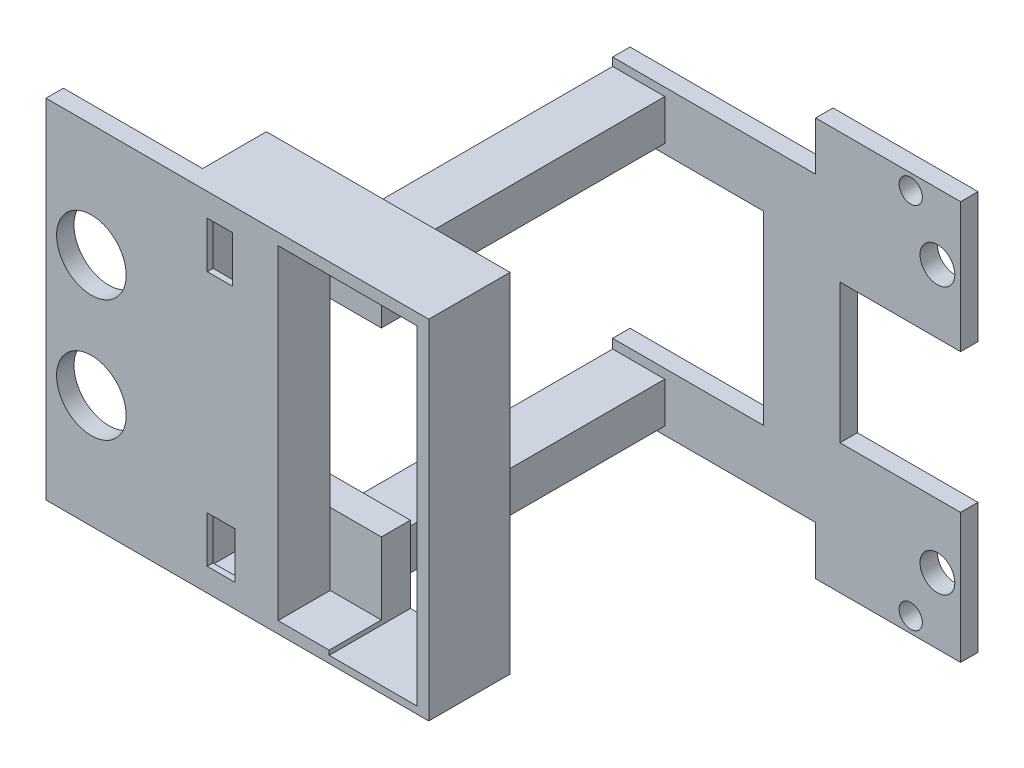
SolidWorks part; units mm, degrees
ref_plane "Front Plane" through (0, 0, 0) normal (0, 0, 1) x (1, 0, 0)
ref_plane "Top Plane" through (0, 0, 0) normal (0, 1, 0) x (1, 0, 0)
ref_plane "Right Plane" through (0, 0, 0) normal (1, 0, 0) x (0, 0, -1)
sketch "Sketch2" plane through (0, 0, 0) normal (0, 0, 1) x (1, 0, 0)
  line L0 (55, 0) -> (-55, 0) construction
  line L1 (-10.5, 15) -> (10.5, 15)
  line L2 (-10.5, 15) -> (-10.5, -15)
  line L3 (-10.5, -15) -> (10.5, -15)
  line L4 (10.5, 15) -> (10.5, -15)
  line L5 (0, -55) -> (0, 55) construction
  point P6 (-10.5, 0)
  point P7 (0, 15)
  dimension "D1" = 30
  dimension "D2" = 21
extrude "Boss-Extrude1" add sketch "Sketch2" along normal blind 7
sketch "Sketch3" plane through (0, 0, 7) normal (0, 0, 1) x (1, 0, 0)
  line L0 (-10.5, 15) -> (-10.5, -15) construction
  line L1 (-2.5, 14) -> (9.5, 14)
  line L2 (-2.5, 14) -> (-2.5, -14)
  line L3 (-2.5, -14) -> (9.5, -14)
  line L4 (9.5, 14) -> (9.5, -14)
  line L6 (10.5, -15) -> (10.5, 15) construction
  line L7 (10.5, 15) -> (-10.5, 15) construction
  line L8 (-10.5, -15) -> (10.5, -15) construction
  dimension "D1" = 8
  dimension "D2" = 1
  dimension "D3" = 1
  dimension "D4" = 1
extrude "Cut-Extrude1" cut sketch "Sketch3" against normal offset from surface (4.5 mm away) 2.5 up to face at (0, 0, 0)
sketch "Sketch4" plane through (0, 0, 0) normal (0, 0, -1) x (-1, 0, 0)
  line L0 (10.5, 15) -> (10.5, -15) construction
  line L1 (5.2688, 14) -> (9.5, 14)
  line L2 (5.2688, 14) -> (5.2688, -14)
  line L3 (5.2688, -14) -> (9.5, -14)
  line L4 (9.5, 14) -> (9.5, -14)
  line L5 (-10.5, 15) -> (10.5, 15) construction
  line L6 (10.5, -15) -> (-10.5, -15) construction
  dimension "D1" = 1
  dimension "D2" = 1
  dimension "D3" = 1
extrude "Cut-Extrude2" cut sketch "Sketch4" against normal offset from surface (6.5 mm away) 0.5 up to face at (3.5, 0, 7)
sketch "Sketch6" plane through (9.5, 0, 0) normal (-1, 0, 0) x (0, 0, 1)
  line L0 (7, 15) -> (7, -15) construction
  line L1 (7, 14) -> (6.5, 14)
  line L2 (7, 14) -> (7, 11.5)
  line L3 (7, 11.5) -> (6.5, 11.5)
  line L4 (6.5, 14) -> (6.5, 11.5)
  line L5 (2.5, 14) -> (7, 14) construction
  line L6 (7, 0) -> (0, 0.978) construction
  line L7 (7, -14) -> (7, 14) construction
  line L8 (3.8481, -11.0596) -> (3.3672, -10.9226)
  line L9 (3.1628, -13.4639) -> (3.8481, -11.0596)
  line L10 (3.1628, -13.4639) -> (2.682, -13.3268)
  line L11 (2.682, -13.3268) -> (3.3672, -10.9226)
  line L12 (0, -11.55) -> (0, 11.55) construction
  point P6 (6.75, 14)
  point P14 (7, 0)
  dimension "D1" = 0.5
  dimension "D2" = 2.5
sketch "Sketch7" plane through (0, 0, 7) normal (0, 0, 1) x (1, 0, 0)
  line L0 (-8.6, 9) -> (-6.4, 9)
  line L1 (-8.6, 13) -> (-6.4, 13)
  line L3 (-8.6, -13) -> (-6.2, -13)
  line L5 (-8.6, -9) -> (-6.2, -9)
  line L6 (-10.5, -15) -> (10.5, -15) construction
  line L7 (10.5, 15) -> (-10.5, 15) construction
  line L8 (-8.6, 13) -> (-8.6, 9)
  line L9 (-6.4, 13) -> (-6.4, 9)
  line L10 (-8.6, -9) -> (-8.6, -13)
  line L11 (-6.2, -9) -> (-6.2, -13)
  line L12 (-10.5, 15) -> (-10.5, -15) construction
  dimension "D1" = 2.2
  dimension "D2" = 4
  dimension "D3" = 2
  dimension "D4" = 2
  dimension "D5" = 4
  dimension "D6" = 2.4
  dimension "D7" = 1.9
  dimension "D8" = 1.9
sketch "Sketch8" plane through (0, 0, 0) normal (0, 0, -1) x (-1, 0, 0)
  line L0 (-10.5, 0) -> (10.5, 0) construction
  line L1 (-3, 12.3) -> (4.5, 12.3)
  line L2 (-3, 12.3) -> (-3, 8.8)
  line L3 (-3, 8.8) -> (4.5, 8.8)
  line L4 (4.5, 12.3) -> (4.5, 8.8)
  line L5 (-3, -8.8) -> (4.5, -8.8)
  line L6 (-3, -8.8) -> (-3, -12.3)
  line L7 (-3, -12.3) -> (4.5, -12.3)
  line L8 (4.5, -8.8) -> (4.5, -12.3)
  line L9 (-10.5, -15) -> (-10.5, 15) construction
  line L10 (10.5, 15) -> (10.5, -15) construction
  point P8 (-3, 10.55)
  point P9 (-3, -10.55)
  dimension "D1" = 21.1
  dimension "D2" = 7.5
  dimension "D3" = 3.5
  dimension "D4" = 7.5
extrude "Boss-Extrude3" add sketch "Sketch8" along normal blind 22.5
sketch "Sketch9" plane through (0, 0, 0) normal (0, 0, -1) x (-1, 0, 0)
  line L0 (5.2688, 14) -> (5.2688, -14) construction
  line L1 (5.2688, -14.6147) -> (-6.9263, -14.6147)
  line L2 (5.2688, -14.6147) -> (5.2688, 13.8175)
  line L3 (5.2688, 13.8175) -> (-6.9263, 13.8175)
  line L4 (-6.9263, -14.6147) -> (-6.9263, 13.8175)
sketch "Sketch10" plane through (0, 0, -22.5) normal (0, 0, -1) x (-1, 0, 0)
  line L0 (-3, 12.3) -> (-3, 8.8) construction
  line L1 (-3, 10.55) -> (4.5, 10.55) construction
  line L2 (4.5, 8.8) -> (4.5, 12.3) construction
  line L3 (3.85, 0) -> (-3.85, 0) construction
  circle A0 centre (0.9, 10.55) radius 0.95
  circle A1 centre (0.9, -10.55) radius 0.95
  dimension "D2" = 1.9
  dimension "D1" = 3.9
extrude "Cut-Extrude4" cut sketch "Sketch10" against normal blind 3
sketch "Sketch11" plane through (0, 0, -22.5) normal (0, 0, -1) x (-1, 0, 0)
  line L0 (4.5, -8.8) -> (-3, -8.8) construction
  line L1 (3.15, -8.8) -> (4.5, -8.8)
  line L2 (3.15, -8.8) -> (3.15, -12.3)
  line L3 (3.15, -12.3) -> (4.5, -12.3)
  line L4 (4.5, -8.8) -> (4.5, -12.3)
  line L5 (-3, -12.3) -> (4.5, -12.3) construction
  line L6 (-1.35, -8.8) -> (-3, -8.8)
  line L7 (-1.35, -8.8) -> (-1.35, -12.3)
  line L8 (-1.35, -12.3) -> (-3, -12.3)
  line L9 (-3, -8.8) -> (-3, -12.3)
  line L10 (-3, -8.8) -> (-3, -12.3) construction
  line L11 (3.85, 0) -> (-3.85, 0) construction
  line L12 (3.15, 12.3) -> (4.5, 12.3)
  line L13 (4.5, 8.8) -> (4.5, 12.3)
  line L14 (3.15, 8.8) -> (4.5, 8.8)
  line L15 (3.15, 8.8) -> (3.15, 12.3)
  line L16 (-1.35, 12.3) -> (-3, 12.3)
  line L17 (-1.35, 8.8) -> (-3, 8.8)
  line L18 (-3, 8.8) -> (-3, 12.3)
  line L19 (-1.35, 8.8) -> (-1.35, 12.3)
  line L20 (0.9, 10.55) -> (0.9, 14.9576) construction
  dimension "D1" = 4.5
extrude "Cut-Extrude5" cut sketch "Sketch11" against normal up to surface (22.5 mm away) up to face at (-0.75, 10.55, 0)
extrude "Cut-Extrude6" cut sketch "Sketch7" against normal blind 2
sketch "Sketch13" plane through (0, 0, 0) normal (0, 0, -1) x (-1, 0, 0)
  line L0 (5.2688, -14.6147) -> (5.2688, 13.8175) construction
  line L1 (5.2688, 7.8) -> (-9.5, 7.8)
  line L2 (5.2688, 7.8) -> (5.2688, -7.8)
  line L3 (5.2688, -7.8) -> (-9.5, -7.8)
  line L4 (-9.5, 7.8) -> (-9.5, -7.8)
  line L5 (-10.5, -15) -> (-10.5, 15) construction
  line L6 (-1.35, 8.8) -> (3.15, 8.8) construction
  line L7 (3.15, -8.8) -> (-1.35, -8.8) construction
  dimension "D1" = 1
  dimension "D2" = 1
  dimension "D3" = 1
extrude "Cut-Extrude8" cut sketch "Sketch13" against normal up to surface (2.5 mm away) up to face at (3.5, 0, 2.5)
sketch "Sketch14" plane through (0, 0, 0) normal (0, 0, -1) x (-1, 0, 0)
  line L0 (-9.5, 14) -> (-9.5, 11.5) construction
  line L1 (-9.5, 14) -> (-1.9145, 14)
  line L2 (-9.5, 14) -> (-9.5, -14.3883)
  line L3 (-9.5, -14.3883) -> (-1.9145, -14.3883)
  line L4 (-1.9145, 14) -> (-1.9145, -14.3883)
extrude "Cut-Extrude9" cut sketch "Sketch14" against normal blind 10
sketch "Sketch15" plane through (0, 0, -22.5) normal (0, 0, -1) x (-1, 0, 0)
  line L0 (3.85, 0) -> (-3.85, 0) construction
  line L1 (3.15, -17.2) -> (-26.85, -17.2)
  line L2 (3.15, -17.2) -> (3.15, 17.2)
  line L3 (3.15, 17.2) -> (-26.85, 17.2)
  line L4 (-26.85, -17.2) -> (-26.85, 17.2)
  line L5 (3.15, -8.8) -> (3.15, -12.3) construction
  point P4 (3.15, 0)
  dimension "D1" = 34.4
  dimension "D2" = 30
extrude "Boss-Extrude4" add sketch "Sketch15" along normal blind 1.5
sketch "Sketch16" plane through (0, 0, -24) normal (0, 0, -1) x (-1, 0, 0)
  line L0 (3.15, -17.2) -> (3.15, 17.2) construction
  line L1 (3.15, 8) -> (-9.85, 8)
  line L2 (3.15, 8) -> (3.15, -8)
  line L3 (3.15, -8) -> (-9.85, -8)
  line L4 (-9.85, 8) -> (-9.85, -8)
  line L5 (3.85, 0) -> (-3.85, 0) construction
  line L6 (3.15, -17.2) -> (3.15, -13)
  line L7 (3.15, 17.2) -> (-14.35, 17.2)
  line L8 (3.15, 17.2) -> (3.15, 13)
  line L9 (3.15, 13) -> (-14.35, 13)
  line L10 (-14.35, 17.2) -> (-14.35, 13)
  line L11 (3.15, -17.2) -> (-14.35, -17.2)
  line L12 (-14.35, -17.2) -> (-14.35, -13)
  line L13 (3.15, -13) -> (-14.35, -13)
  line L14 (-26.85, 17.2) -> (-26.85, -17.2) construction
  line L15 (-26.85, 6) -> (-16.45, 6)
  line L16 (-26.85, 6) -> (-26.85, -6)
  line L17 (-26.85, -6) -> (-16.45, -6)
  line L18 (-16.45, 6) -> (-16.45, -6)
  point P6 (3.15, 0)
  point P24 (-26.85, 0)
  dimension "D1" = 16
  dimension "D2" = 13
  dimension "D3" = 17.5
  dimension "D4" = 4.2
  dimension "D5" = 12
  dimension "D6" = 10.4
extrude "Cut-Extrude10" cut sketch "Sketch16" against normal blind 2
sketch "Sketch17" plane through (0, 0, -24) normal (0, 0, -1) x (-1, 0, 0)
  line L0 (-9.85, 8) -> (-9.85, -8) construction
  line L1 (3.85, 0) -> (-3.85, 0) construction
  circle A0 centre (-22.55, -15.875) radius 1
  circle A1 centre (-24.85, -11.5) radius 1.5
  circle A2 centre (-22.55, 15.875) radius 1
  circle A3 centre (-24.85, 11.5) radius 1.5
  dimension "D3" = 3
  dimension "D4" = 2
  dimension "D1" = 12.7
  dimension "D2" = 15
  dimension "D5" = 23
  dimension "D6" = 31.75
extrude "Cut-Extrude11" cut sketch "Sketch17" against normal blind 2
sketch "Sketch18" plane through (-10.5, 0, 0) normal (-1, 0, 0) x (0, 0, 1)
  line L0 (7, -15) -> (0, -15) construction
  line L1 (7, 15) -> (5.5, 15)
  line L2 (7, 15) -> (7, -15)
  line L3 (7, -15) -> (5.5, -15)
  line L4 (5.5, 15) -> (5.5, -15)
  dimension "D1" = 1.5
extrude "Boss-Extrude5" add sketch "Sketch18" along normal blind 12
sketch "Sketch19" plane through (0, 0, 5.5) normal (0, 0, -1) x (-1, 0, 0)
  line L0 (17.05, 0) -> (-17.05, 0) construction
  line L1 (21.5437, 0) -> (-29.3345, 0) construction
  line L2 (22.5, -15) -> (22.5, 0) construction
  line L3 (22.5, 15) -> (22.5, -15) construction
  line L4 (22.5, 0) -> (22.5, 15) construction
  circle A0 centre (18.589, 5.2438) radius 3
  circle A1 centre (18.589, -5.2438) radius 3
  dimension "D1" = 6
  dimension "D2" = 6
extrude "Cut-Extrude12" cut sketch "Sketch19" against normal blind 10
